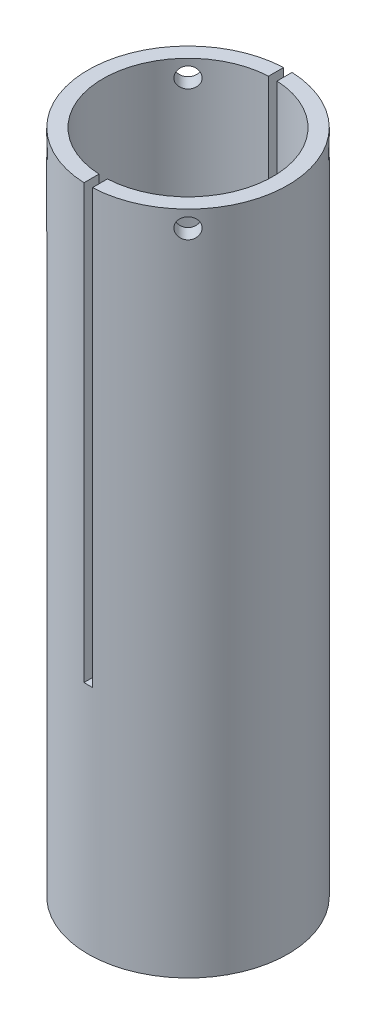
SolidWorks part; units mm, degrees
material "Brass"
ref_plane "Front Plane" through (0, 0, 0) normal (0, 0, 1) x (1, 0, 0)
ref_plane "Top Plane" through (0, 0, 0) normal (0, 1, 0) x (1, 0, 0)
ref_plane "Right Plane" through (0, 0, 0) normal (1, 0, 0) x (0, 0, -1)
sketch "Sketch1" plane through (0, 0, 0) normal (0, 1, 0) x (1, 0, 0)
  circle A0 centre (0, 0) radius 3
  circle A1 centre (0, 0) radius 2.55
  dimension "D1" = 6
  dimension "D2" = 0.45
extrude "Boss-Extrude1" add sketch "Sketch1" along normal blind 20
sketch "Sketch2" plane through (0, 0, 0) normal (0, 0, 1) x (1, 0, 0)
  line L0 (2.55, 20) -> (-2.55, 20) construction
  line L1 (-0.127, 20) -> (0.127, 20)
  line L2 (-0.127, 20) -> (-0.127, 7)
  line L3 (-0.127, 7) -> (0.127, 7)
  line L4 (0.127, 20) -> (0.127, 7)
  line L5 (-0.127, 20) -> (0.127, 7) construction
  line L6 (-0.127, 7) -> (0.127, 20) construction
  point P0 (0, 13.5)
  dimension "D1" = 13
  dimension "D2" = 0.254
extrude "Cut-Extrude1" cut sketch "Sketch2" against normal through all and the other way through all
hole_wizard "Ø0.6 (0.6) Diameter Hole1" positions "3DSketch1" profile "Sketch3" hole size "Ø0.6" standard "ANSI Metric" end condition up to next
sketch3d "3DSketch1"
  line L0 (0, 20, 0) -> (0, 19.5, 0) construction
  line L1 (0, 19.5, 0) -> (2.1213, 19.5, -2.1213) construction
  line L4 (0, 19.5, 0) -> (2.1213, 19.5, 2.1213) construction
  line L5 (2.1213, 19.5, 2.1213) -> (2.1213, 19.5, -2.1213) construction
  line L6 (0, 19.5, 0) -> (-2.1213, 19.5, 2.1213) construction
  line L9 (0, 19.5, 0) -> (-2.1213, 19.5, -2.1213) construction
  arc A0 (-0.127, 20, -2.9973) -> (-0.127, 20, 2.9973) centre (0, 20, 0) ccw construction
  point P15 (0, 23, 0)
  point P16 (2.1213, 19.5, 2.1213)
  point P18 (2.1213, 19.5, -2.1213)
  point P29 (-2.1213, 19.5, 2.1213)
  point P31 (-2.1213, 19.5, -2.1213)
  dimension "D1" = 0.5
sketch "Sketch3" plane through (2.1213, 19.5, 2.1213) normal (0, 1, 0) x (0.7071, 0, -0.7071)
  line L0 (0, 0) -> (0, 0.45)
  line L1 (0, 0.45) -> (0.3, 0.45)
  line L2 (0.3, 0.45) -> (0.3, 0)
  line L5 (0.3, 0) -> (0, 0)
  line L11 (0, -6.35) -> (0, 107.95) construction
  dimension "Thru Hole Dia." = 0.6
  dimension "Thru Hole Depth" = 0.45
